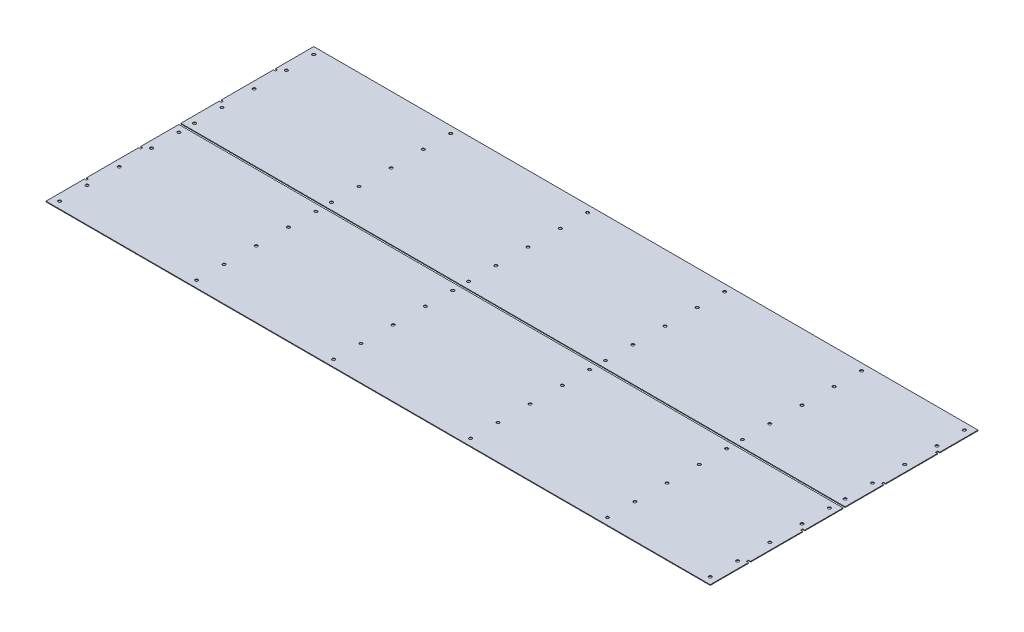
SolidWorks part; units mm, degrees
ref_plane "Front Plane" through (0, 0, 0) normal (0, 0, 1) x (1, 0, 0)
ref_plane "Top Plane" through (0, 0, 0) normal (0, 1, 0) x (1, 0, 0)
ref_plane "Right Plane" through (0, 0, 0) normal (1, 0, 0) x (0, 0, -1)
sketch "Sketch1" plane through (0, 0, 0) normal (0, 1, 0) x (1, 0, 0)
  line L0 (-10, -41) -> (-10, -97)
  line L1 (-10, -97) -> (960, -97)
  line L2 (960, -97) -> (960, -41)
  line L3 (960, -41) -> (-10, -41) construction
  line L4 (0, 0) -> (-7, 0) construction
  line L5 (-10, -41) -> (-7, -41)
  line L7 (-7, 41) -> (-10, 41)
  line L8 (-10, 41) -> (-10, 97)
  line L9 (-10, 97) -> (960, 97)
  line L10 (960, 97) -> (960, 41)
  line L11 (960, 41) -> (957, 41)
  line L13 (957, -41) -> (960, -41)
  line L14 (0, 47) -> (950, 47) construction
  line L15 (-7, 41) -> (-7, 38)
  line L16 (-7, 41) -> (957, 41) construction
  line L17 (957, 41) -> (957, -41) construction
  line L18 (-7, 41) -> (-7, -41) construction
  line L19 (-7, 38) -> (-10, 38)
  line L20 (-10, 38) -> (-10, -38)
  line L21 (-10, -38) -> (-7, -38)
  line L22 (-7, -38) -> (-7, -41)
  line L23 (957, 41) -> (957, 38)
  line L24 (957, 38) -> (960, 38)
  line L25 (960, 38) -> (960, -38)
  line L26 (960, -38) -> (957, -38)
  line L27 (957, -38) -> (957, -41)
  line L28 (960, 0) -> (957, 0) construction
  line L29 (950, 47) -> (950, -47) construction
  line L30 (-7, 0) -> (-10, 0) construction
  line L31 (0, 47) -> (0, -47) construction
  line L32 (950, -47) -> (0, -47) construction
  line L33 (0, 47) -> (0, 87) construction
  line L34 (0, 87) -> (950, 87) construction
  line L35 (950, 87) -> (950, 47) construction
  line L36 (950, -47) -> (950, -87) construction
  line L37 (950, -87) -> (0, -87) construction
  line L38 (0, -87) -> (0, -47) construction
  line L39 (0, 0) -> (950, 0) construction
  line L40 (200, 87) -> (200, 47) construction
  line L41 (200, 47) -> (200, 0) construction
  line L42 (200, 0) -> (200, -47) construction
  line L43 (200, -47) -> (200, -87) construction
  circle A0 centre (0, -47) radius 2.15
  circle A30 centre (0, 47) radius 2.15
  circle A31 centre (0, -87) radius 2.15
  circle A32 centre (0, 87) radius 2.15
  circle A33 centre (200, -87) radius 2.15
  circle A34 centre (200, -47) radius 2.15
  circle A35 centre (200, 47) radius 2.15
  circle A36 centre (200, 87) radius 2.15
  circle A37 centre (400, -87) radius 2.15
  circle A38 centre (400, -47) radius 2.15
  circle A39 centre (400, 47) radius 2.15
  circle A40 centre (400, 87) radius 2.15
  circle A41 centre (600, -87) radius 2.15
  circle A42 centre (600, -47) radius 2.15
  circle A43 centre (600, 47) radius 2.15
  circle A44 centre (600, 87) radius 2.15
  circle A45 centre (800, -87) radius 2.15
  circle A46 centre (800, -47) radius 2.15
  circle A47 centre (800, 47) radius 2.15
  circle A48 centre (800, 87) radius 2.15
  circle A53 centre (0, 0) radius 2.15
  circle A54 centre (950, 0) radius 2.15
  circle A55 centre (200, 0) radius 2.15
  circle A56 centre (400, 0) radius 2.15
  circle A57 centre (600, 0) radius 2.15
  circle A58 centre (800, 0) radius 2.15
  circle A59 centre (950, 87) radius 2.15
  circle A60 centre (950, 47) radius 2.15
  circle A61 centre (950, -47) radius 2.15
  circle A62 centre (950, -87) radius 2.15
  point P17 (0, 67)
  dimension "D1" = 3
  dimension "D12" = 4.3
  dimension "D9" = 5
  dimension "D3" = 6
  dimension "D4" = 10
  dimension "D5" = 10
  dimension "D6" = 40
  dimension "D7" = 10
  dimension "D8" = 3
  dimension "D2" = 76
  dimension "D10" = 970
  dimension "D15" = 200
  dimension "D14" = 5
extrude "Boss-Extrude1" add sketch "Sketch1" along normal blind 1
pattern_linear "LPattern2" count 2 spacing 197 along (0, 0, -1) of bodies 101
